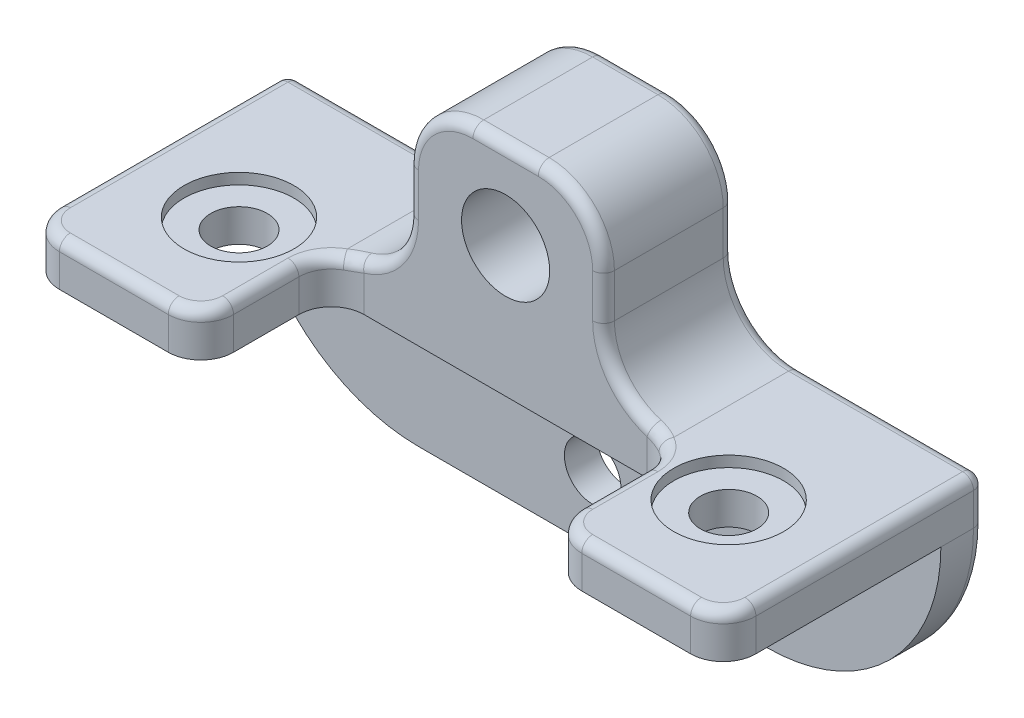
SolidWorks part; units mm, degrees
ref_plane "Front Plane" through (0, 0, 0) normal (0, 0, 1) x (1, 0, 0)
ref_plane "Top Plane" through (0, 0, 0) normal (0, 1, 0) x (1, 0, 0)
ref_plane "Right Plane" through (0, 0, 0) normal (1, 0, 0) x (0, 0, -1)
sketch "Sketch1" plane through (0, 0, 0) normal (0, 1, 0) x (1, 0, 0)
  line L1 (0, 0) -> (58, 0)
  line L2 (0, 0) -> (0, 20)
  line L3 (0, 20) -> (58, 20)
  line L4 (58, 0) -> (58, 20)
  dimension "D1" = 20
  dimension "D2" = 58
extrude "Boss-Extrude1" add sketch "Sketch1" along normal blind 4
sketch "Sketch2" plane through (0, 4, 0) normal (0, 1, 0) x (1, 0, 0)
  line L0 (58, 20) -> (0, 20) construction
  line L1 (20, 20) -> (38, 20)
  line L2 (20, 20) -> (20, 0)
  line L3 (20, 0) -> (38, 0)
  line L4 (38, 20) -> (38, 0)
  line L5 (0, 0) -> (58, 0) construction
  point P8 (29, 0)
  point P9 (29, 0)
  dimension "D1" = 18
extrude "Boss-Extrude2" add sketch "Sketch2" along normal blind 16
sketch "Sketch3" plane through (0, 0, 0) normal (0, 0, 1) x (1, 0, 0)
  line L0 (20, 20) -> (38, 20) construction
  line L1 (0, 0) -> (58, 0) construction
  circle A0 centre (29, 12) radius 4.05
  point P5 (29, 20)
  dimension "D1" = 8.1
  dimension "D2" = 12
extrude "Cut-Extrude1" cut sketch "Sketch3" against normal through all
sketch "Sketch4" plane through (0, 4, 0) normal (0, 1, 0) x (1, 0, 0)
  line L0 (6.5, 10) -> (51.5, 10) construction
  line L1 (58, 0) -> (58, 20) construction
  line L2 (20, 0) -> (38, 0) construction
  line L3 (20, 20) -> (0, 20) construction
  circle A0 centre (6.5, 10) radius 2.6
  circle A1 centre (51.5, 10) radius 2.6
  point P7 (29, 10)
  point P10 (29, 0)
  dimension "D1" = 5.2
  dimension "D2" = 6.5
  dimension "D3" = 10
extrude "Cut-Extrude2" cut sketch "Sketch4" against normal blind 16
sketch "Sketch5" plane through (0, 4, 0) normal (0, 1, 0) x (1, 0, 0)
  line L3 (13, 0) -> (45, 0)
  line L4 (45, 12) -> (45, 0)
  line L5 (20, 0) -> (38, 0) construction
  line L6 (13, 0) -> (13, 12)
  line L7 (13, 12) -> (45, 12)
  point P9 (29, 0)
  point P10 (29, 0)
  dimension "D1" = 32
  dimension "D2" = 12
extrude "Cut-Extrude3" cut sketch "Sketch5" against normal through all both and the other way through all
sketch "Sketch6" plane through (0, 4, 0) normal (0, 1, 0) x (1, 0, 0)
  line L0 (58, 0) -> (58, 20) construction
  line L1 (0, 20) -> (58, 20)
  line L2 (0, 20) -> (0, 24)
  line L3 (0, 24) -> (58, 24)
  line L4 (58, 20) -> (58, 24)
  dimension "D1" = 4
extrude "Boss-Extrude3" add sketch "Sketch6" against normal blind 20
sketch "Sketch7" plane through (0, 0, -20) normal (0, 0, -1) x (-1, 0, 0)
  line L1 (-38, 20) -> (-20, 20)
  line L2 (-38, 20) -> (-38, 4)
  line L3 (-38, 4) -> (-20, 4)
  line L4 (-20, 20) -> (-20, 4)
extrude "Boss-Extrude4" add sketch "Sketch7" along normal blind 4
sketch "Sketch12" plane through (0, 0, 0) normal (0, -1, 0) x (1, 0, 0)
  line L0 (45, 0) -> (58, 0) construction
  line L1 (58, -24) -> (61, -24)
  line L2 (58, -24) -> (58, 0)
  line L3 (58, 0) -> (61, 0)
  line L4 (61, -24) -> (61, 0)
  line L5 (0, -24) -> (-3, -24)
  line L6 (0, -24) -> (0, 0)
  line L7 (0, 0) -> (-3, 0)
  line L8 (-3, -24) -> (-3, 0)
  dimension "D1" = 3
extrude "Boss-Extrude5" add sketch "Sketch12" against normal up to surface (4 mm away) up to face at (51.5, 4, -7.4)
sketch "Sketch13" plane through (0, 0, 0) normal (0, -1, 0) x (1, 0, 0)
  line L1 (58, -20) -> (61, -20)
  line L2 (58, -20) -> (58, -24)
  line L3 (58, -24) -> (61, -24)
  line L4 (61, -20) -> (61, -24)
  line L5 (0, -20) -> (-3, -20)
  line L6 (0, -20) -> (0, -24)
  line L7 (0, -24) -> (-3, -24)
  line L8 (-3, -20) -> (-3, -24)
extrude "Boss-Extrude6" add sketch "Sketch13" along normal up to surface (16 mm away) up to face at (29, -16, -22)
fillet "Fillet1" radius 6 4 edges at (38, 20, -18) (20, 20, -18) (20, 4, -18) (38, 4, -18)
fillet "Fillet2" radius 3 6 edges at (45, 2, -12) (13, 2, -12) (45, 2, 0) (13, 2, 0) (-3, 2, 0) (61, 2, 0)
fillet "Fillet3" radius 16 2 edges at (-3, -16, -22) (61, -16, -22)
sketch "Sketch8" plane through (0, 0, -20) normal (0, 0, 1) x (1, 0, 0)
  line L0 (42, 0) -> (16, 0) construction
  circle A0 centre (29, -10) radius 2.6
  point P4 (29, 0)
  dimension "D2" = 5.2
  dimension "D1" = 10
extrude "Cut-Extrude4" cut sketch "Sketch8" against normal blind 4
fillet "Fillet4" radius 1 34 edges at (29, -16, -24) (5, 4, 0) (45.8787, 4, -0.8787) (45, 4, -6) (44.7386, 4, -10.2247) (42.8946, 4.1027, -11.8635) (39.101, 6.5359, -12) (38, 12, -12) (36.2426, 18.2426, -12) (29, 20, -12) (21.7574, 18.2426, -12) (20, 12, -12) (18.899, 6.5359, -12) (14.7854, 4.0516, -11.7431) (13.2614, 4, -10.2247) (13, 4, -6) (12.1213, 4, -0.8787) (5.5, 4, -24) (18.2426, 5.7574, -24) (20, 12, -24) (52.5, 4, -24) (39.7574, 5.7574, -24) (38, 12, -24) (36.2426, 18.2426, -24) (29, 20, -24) (21.7574, 18.2426, -24) (61, 2, -24) (56.3137, -11.3137, -24) (-3, 2, -24) (1.6863, -11.3137, -24) (-3, 4, -13.5) (-2.1213, 4, -0.8787) (61, 4, -13.5) (60.1213, 4, -0.8787)
sketch "Sketch9" plane through (0, 4, 0) normal (0, 1, 0) x (1, 0, 0)
  circle A0 centre (6.5, 10) radius 5.05
  circle A1 centre (51.5, 10) radius 5.05
  circle A2 centre (51.5, 10) radius 2.6 construction
  circle A3 centre (6.5, 10) radius 2.6 construction
  dimension "D1" = 10.1
extrude "Cut-Extrude5" cut sketch "Sketch9" against normal blind 1
sketch "Sketch10" plane through (0, 0, -24) normal (0, 0, -1) x (-1, 0, 0)
  circle A0 centre (-29, -10) radius 5.05
  dimension "D1" = 10.1
extrude "Cut-Extrude6" cut sketch "Sketch10" against normal blind 1
sketch "Sketch11" plane through (0, 0, -20) normal (0, 0, 1) x (1, 0, 0)
  circle A0 centre (29, 12) radius 1
  dimension "D1" = 2
extrude "Cut-Extrude7" cut sketch "Sketch11" against normal through all
